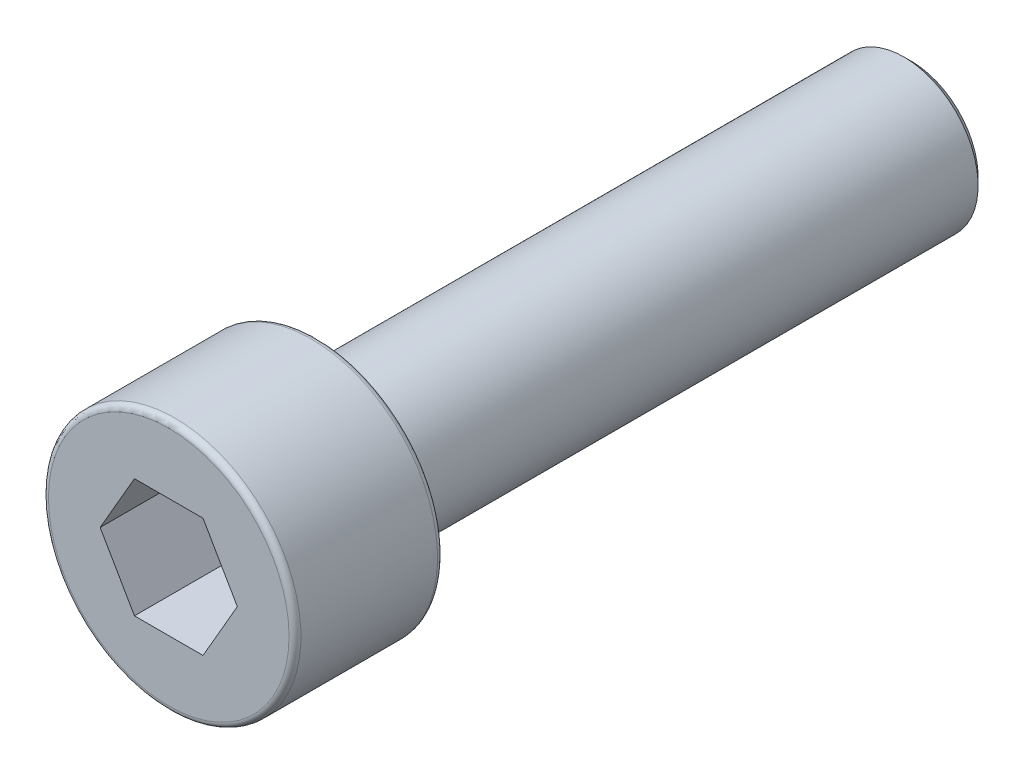
SolidWorks part; units mm, degrees
ref_plane "Front Plane" through (0, 0, 0) normal (0, 0, 1) x (1, 0, 0)
ref_plane "Top Plane" through (0, 0, 0) normal (0, 1, 0) x (1, 0, 0)
ref_plane "Right Plane" through (0, 0, 0) normal (1, 0, 0) x (0, 0, -1)
ref_plane "Plane1" through (0, 0, 25) normal (0, 0, 1) x (1, 0, 0)
sketch "Sketch1" plane through (0, 0, 25) normal (0, 0, 1) x (1, 0, 0)
  circle A0 centre (0, 0) radius 4.25
extrude "Boss-Extrude1" add sketch "Sketch1" against normal blind 5
sketch "Sketch2" plane through (0, 0, 20) normal (0, 0, -1) x (-1, 0, 0)
  circle A0 centre (0, 0) radius 2.5
extrude "Boss-Extrude2" add sketch "Sketch2" along normal blind 20
sketch "Sketch3" plane through (0, 0, 25) normal (0, 0, 1) x (1, 0, 0)
  line L0 (-2.3094, 0) -> (-1.1547, -2)
  line L1 (-1.1547, -2) -> (1.1547, -2)
  line L2 (1.1547, -2) -> (2.3094, 0)
  line L3 (2.3094, 0) -> (1.1547, 2)
  line L4 (1.1547, 2) -> (-1.1547, 2)
  line L5 (-1.1547, 2) -> (-2.3094, 0)
extrude "Cut-Extrude1" cut sketch "Sketch3" against normal blind 4
chamfer "Chamfer1" distance 0.25 angle 45 1 edges at (-2.5, 0, 0)
fillet "Fillet1" radius 0.2 2 edges at (-4.25, 0, 20) (-4.25, 0, 25) tangent propagation no
ref_axis "Axis1" through (0, 0, -3.2315) along (0, 0, 1)
